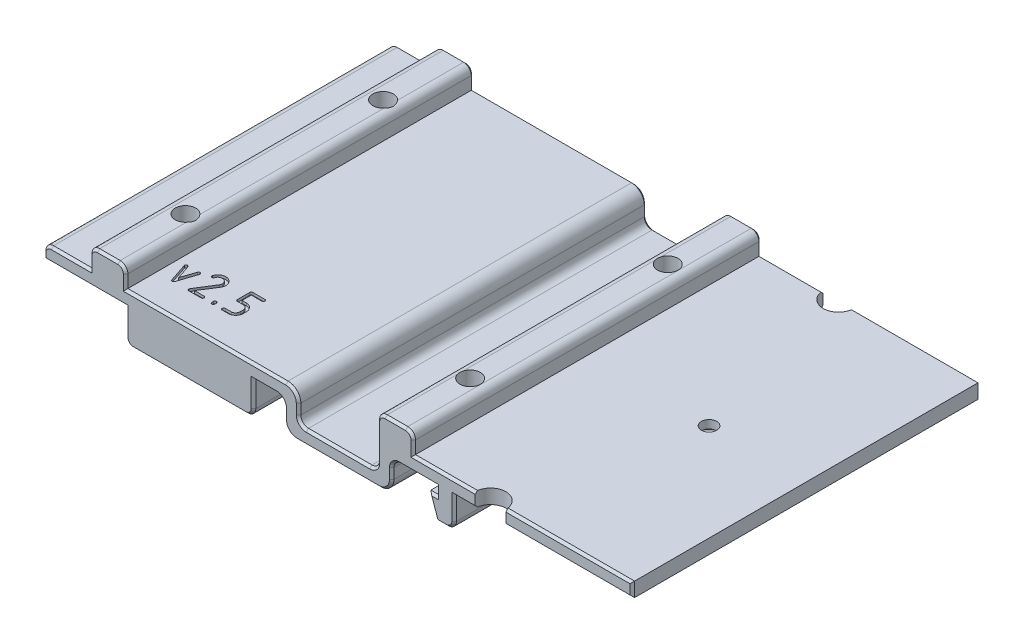
SolidWorks part; units mm, degrees
note: '?' marks a value the reader was unsure of.
material "ABS_eSun_GRN"
ref_plane "Front Plane" through (0, 0, 0) normal (0, 0, 1) x (1, 0, 0)
ref_plane "Top Plane" through (0, 0, 0) normal (0, 1, 0) x (1, 0, 0)
ref_plane "Right Plane" through (0, 0, 0) normal (1, 0, 0) x (0, 0, -1)
sketch "Sketch1" plane through (0, 0, 0) normal (0, 0, 1) x (1, 0, 0)
  line L1 (-18.2, 0) -> (-18.2, -6.5)
  line L4 (-18.2, -6.5) -> (-43.2, -6.5)
  line L6 (-59.2, 2.8) -> (-9.4, 2.8)
  line L19 (-12.2, 0) -> (-18.2, 0)
  line L20 (-12.2, 0) -> (-12.2, -6)
  line L21 (-12.2, -6) -> (8.8, -6)
  line L27 (-9.4, 2.8) -> (-9.4, -3.2)
  line L29 (21, -6) -> (17.5, -6)
  line L33 (17.5, -1.7) -> (17.5, 0)
  line L34 (17.5, -1.7) -> (16, -1.7)
  line L35 (16, -1.7) -> (17.5, -6)
  line L37 (-43.2, -6.5) -> (-43.2, 0)
  line L40 (21, 0) -> (21, -6)
  line L42 (8.8, 0) -> (17.5, 0)
  line L43 (8.8, -6) -> (8.8, 0)
  line L44 (-9.4, -3.2) -> (6, -3.2)
  line L45 (6, -3.2) -> (6, 2.8)
  line L46 (6, 2.8) -> (21.0725, 2.8)
  line L47 (6, -3.2) -> (6, -6) construction
  line L48 (6, -3.2) -> (8.8, -3.2) construction
  line L49 (-9.4, -3.2) -> (-12.2, -3.2) construction
  line L50 (8.8, 0) -> (8.8, 2.8) construction
  line L51 (21, 0) -> (55.8, 0)
  line L52 (55.8, 0) -> (55.8, 2.8)
  line L53 (55.8, 2.8) -> (21.0725, 2.8)
  line L54 (-43.2, 0) -> (-59.2, 0)
  line L55 (-59.2, 0) -> (-59.2, 2.8)
  line L56 (8.8, 0) -> (8.8, 11.1094) construction
  dimension "D1" = 35.7
  dimension "D6" = 1.5
  dimension "D16" = 6
  dimension "D3" = 6.5
  dimension "D5" = 1.7
  dimension "D4" = 3.5
  dimension "D2" = 2.8
  dimension "D7" = 6
  dimension "D10" = 16
  dimension "D11" = 25
  dimension "D9" = 115
  dimension "D8" = 18.2
  dimension "D12" = 6
extrude "mainBody" add sketch "Sketch1" along normal mid plane 68
ref_axis "AXIS-PRINT" through (0, 0, -22) along (0, 0, 1)?
fillet "fillet_corners_inside" radius 1.5 8 edges at (-43.2, -6.5, 0) (21, -6, 0) (-18.2, -6.5, 0) (6, -3.2, 0) (-9.4, -3.2, 0) (8.8, 0, 0) (-12.2, 0, 0) (-59.2, 2.8, 0)
fillet "fillet_corners_outside" radius 2.5 3 edges at (8.8, -6, 0) (-12.2, -6, 0) (-9.4, 2.8, 0)
ref_plane "PLANE_SPRNG" through (0, -2.3, 0) normal (0, 1, 0) x (1, 0, 0)
sketch "Sketch2" plane through (0, -2.3, 0) normal (0, 1, 0) x (1, 0, 0)
  line L0 (-44, 6.5) -> (-27.5, 7.5)
  line L1 (-27.5, 7.5) -> (-20.5, 11)
  line L4 (-27.5, -7.5) -> (-44, -6.5)
  line L5 (-44, -6.5) -> (-44, 6.5)
  line L6 (-27.5, 7.5) -> (-27.5, -7.5) construction
  line L8 (-20.5, 11) -> (-20.5, 16.5)
  line L9 (-20.5, 16.5) -> (-18.2, 16.5)
  line L10 (-18.2, -34) -> (-18.2, 34) construction
  line L11 (-18.2, 16.5) -> (-18.2, -16.5)
  line L12 (-18.2, -16.5) -> (-20.5, -16.5)
  line L13 (-20.5, -16.5) -> (-20.5, -11)
  line L14 (-20.5, 11) -> (-20.5, -11) construction
  line L15 (-41.7, -34) -> (-41.7, 34) construction
  line L16 (-20.5, -11) -> (-27.5, -7.5)
  point P2 (-44, 0)
  point P3 (-18.2, 0)
  point P4 (-27.5, 0)
  dimension "D1" = 2.3
  dimension "D2" = 15
  dimension "D3" = 7
  dimension "D4" = 33
  dimension "D5" = 22
  dimension "D6" = 13
  dimension "D7" = 2.3
extrude "spring_slot" cut sketch "Sketch2" against normal mid plane 2.1
sketch "Sketch4" plane through (0, -6.5, 0) normal (0, -1, 0) x (1, 0, 0)
  line L0 (-43.2, 4.5448) -> (-26.9711, 5.5284)
  line L1 (-43.2, -34) -> (-43.2, 34) construction
  line L2 (-26.9711, 5.5284) -> (-17, 10.5139)
  line L4 (-17, 10.5139) -> (-17, -10.5139)
  line L5 (-17, -10.5139) -> (-26.9711, -5.5284)
  line L6 (-26.9711, -5.5284) -> (-43.2, -4.5448)
  line L7 (-43.2, -4.5448) -> (-43.2, 4.5448)
  line L8 (-43.2, 6.5485) -> (-27.5, 7.5) construction
  line L10 (-27.5, 7.5) -> (-20.5, 11) construction
  line L11 (-20.5, -11) -> (-27.5, -7.5) construction
  point P6 (-17, 0)
  point P16 (-43.2, 0)
  dimension "D1" = 2
  dimension "D2" = 2
  dimension "D3" = 17
extrude "spring_entry" cut sketch "Sketch4" against normal up to surface (5.25 mm away) up to face at (-25.98, -1.25, 0)
sketch "5mmHoles" plane through (0, 0, 0) normal (0, 1, 0) x (1, 0, 0)
  circle A0 centre (5, 0) radius 2.7
  circle A1 centre (-25, 0) radius 2.7
  dimension "D1" = 5.4
  dimension "D2" = 5
  dimension "D3" = 25
fillet "Fillet2" radius 8 2 edges at (-26.9711, -4.925, 5.5284) (-26.9711, -4.925, -5.5284)
sketch "Sketch5" plane through (0, 2.8, 0) normal (0, 1, 0) x (1, 0, 0)
  line L0 (-42.2, -28) -> (-14.5357, -28) construction
  line L3 (-59.2, -34) -> (-59.2, 34) construction
  text T0 "v2.5" font "DS ISO 1" height 6
  dimension "D2" = 17
extrude "cut_version" cut sketch "Sketch5" against normal blind 0.5
sketch "Sketch7" plane through (0, 0, 0) normal (0, 1, 0) x (1, 0, 0)
  line L0 (55.8, -34) -> (55.8, 34) construction
  circle A0 centre (36.8, 0) radius 1.5
  dimension "D3" = 3
  dimension "D1" = 19
extrude "panel_hole" cut sketch "Sketch7" along normal blind 10
sketch "Sketch10" plane through (0, 0, 0) normal (0, -1, 0) x (1, 0, 0)
  circle A0 centre (36.8, 0) radius 3
  dimension "D1" = 6
extrude "counterBore" cut sketch "Sketch10" against normal blind 1.2
sketch "Sketch11" plane through (0, 0, 0) normal (0, 0, 1) x (1, 0, 0)
  line L0 (-11.9, 2.8) -> (-57.7, 2.8) construction
  line L1 (-50.2, 2.8) -> (-43.2, 2.8)
  line L2 (-50.2, 2.8) -> (-50.2, 6.8)
  line L3 (-50.2, 6.8) -> (-43.2, 6.8)
  line L4 (-43.2, 2.8) -> (-43.2, 6.8)
  line L5 (55.8, 2.8) -> (6, 2.8) construction
  line L6 (6, 2.8) -> (13, 2.8)
  line L7 (6, 2.8) -> (6, 6.8)
  line L8 (6, 6.8) -> (13, 6.8)
  line L9 (13, 2.8) -> (13, 6.8)
  line L10 (-59.2, 1.3) -> (-59.2, 0) construction
  point P14 (-46.7, 6.8)
  point P15 (9.5, 6.8)
  dimension "D1" = 7
  dimension "D2" = 12.5
  dimension "D3" = 9.5
  dimension "D4" = 4
extrude "Boss-Extrude2" add sketch "Sketch11" along normal mid plane 68
sketch "Sketch9" plane through (0, 0, 0) normal (0, 1, 0) x (1, 0, 0)
  line L1 (-46.2, 19.305) -> (9.43, 19.305) construction
  line L2 (-46.2, 19.305) -> (-46.2, -19.305) construction
  line L3 (-46.2, -19.305) -> (9.43, -19.305) construction
  line L4 (9.43, 19.305) -> (9.43, -19.305) construction
  circle A0 centre (-46.2, 19.305) radius 2
  circle A1 centre (9.43, 19.305) radius 2
  circle A2 centre (9.43, -19.305) radius 2
  circle A3 centre (-46.2, -19.305) radius 2
  point P8 (-46.2, 0)
  dimension "D1" = 4
  dimension "D2" = 38.61
  dimension "D3" = 55.63
extrude "holes_batMount" cut sketch "Sketch9" along normal through all both and the other way through all contours A0
fillet "Fillet3" radius 1.5 4 edges at (13, 6.8, 0) (6, 6.8, 0) (-43.2, 6.8, 0) (-50.2, 6.8, 0)
chamfer "chamf_face" distance 0.45 angle 45 86 edges at (-30.7, -6.5, 34) (-30.7, -6.5, -34) (-18.2, -2.5, -34) (-18.2, -2.5, 34) (-15.95, 0, -34) (-15.95, 0, 34) (-12.2, -2.5, -34) (-12.2, -2.5, 34) (-1.7, -6, -34) (-1.7, -6, 34) (17.5, -0.85, -34) (17.5, -0.85, 34) (16.75, -1.7, -34) (16.75, -1.7, 34) (16.75, -3.85, -34) (16.75, -3.85, 34) (18.5, -6, -34) (18.5, -6, 34) (-43.2, -2.5, 34) (-43.2, -2.5, -34) (21, -2.25, 34) (21, -2.25, -34) (-42.7607, -6.0607, -34) (-42.7607, -6.0607, 34) (13.9, 0, -34) (13.9, 0, 34) (20.5607, -5.5607, 34) (20.5607, -5.5607, -34) (8.8, -2.5, -34) (8.8, -2.5, 34) (-9.4, -0.7, -34) (-9.4, -0.7, 34) (-1.7, -3.2, 34) (-1.7, -3.2, -34) (6, 1.8, 34) (6, 1.8, -34) (34.4, 2.8, 34) (34.4, 2.8, -34) (-8.9607, -2.7607, 34) (-8.9607, -2.7607, -34) (5.5607, -2.7607, 34) (5.5607, -2.7607, -34) (-18.6393, -6.0607, 34) (-18.6393, -6.0607, -34) (9.2393, -0.4393, -34) (9.2393, -0.4393, 34) (-12.6393, -0.4393, 34) (-12.6393, -0.4393, -34) (-11.4678, -5.2678, 34) (-11.4678, -5.2678, -34) (-10.1322, 2.0678, 34) (-10.1322, 2.0678, -34) (8.0678, -5.2678, 34) (8.0678, -5.2678, -34) (55.8, 1.4, -34) (55.8, 1.4, 34) (38.4, 0, -34) (38.4, 0, 34) (-51.2, 0, -34) (-51.2, 0, 34) (-59.2, 0.65, 34) (-59.2, 0.65, -34) (-58.7607, 2.3607, 34) (-58.7607, 2.3607, -34) (-53.95, 2.8, -34) (-53.95, 2.8, 34) (-50.2, 4.05, 34) (-50.2, 4.05, -34) (-46.7, 6.8, 34) (-46.7, 6.8, -34) (-43.2, 4.05, -34) (-43.2, 4.05, 34) (-27.55, 2.8, 34) (-27.55, 2.8, -34) (9.5, 6.8, 34) (9.5, 6.8, -34) (13, 4.05, -34) (13, 4.05, 34) (-49.7607, 6.3607, 34) (-49.7607, 6.3607, -34) (-43.6393, 6.3607, 34) (-43.6393, 6.3607, -34) (6.4393, 6.3607, -34) (6.4393, 6.3607, 34) (12.5607, 6.3607, 34) (12.5607, 6.3607, -34)
sketch "Sketch12" plane through (0, 0, 0) normal (0, 1, 0) x (1, 0, 0)
  line L2 (55.35, -34) -> (12.55, -34) construction
  circle A2 centre (28.0969, -34) radius 3
  dimension "D1" = 6
extrude "Cut-Extrude1" cut sketch "Sketch12" against normal through all both and the other way through all
mirror "Mirror1" about plane through (0, 0, 0) normal (0, 0, 1) of "Cut-Extrude1"
equation "\"width\"=68"
equation "\"D1@mainBody\"=\"width\""
equation "\"diam_holes\"=4"
equation "\"thickness_A\"=2.8"
equation "\"D2@Sketch1\"=\"thickness_A\""
equation "\"widthDIN\"=17"
equation "\"D3@Sketch4\"=\"widthDIN\""
equation "\"D1@Boss-Extrude2\"=\"width\""
